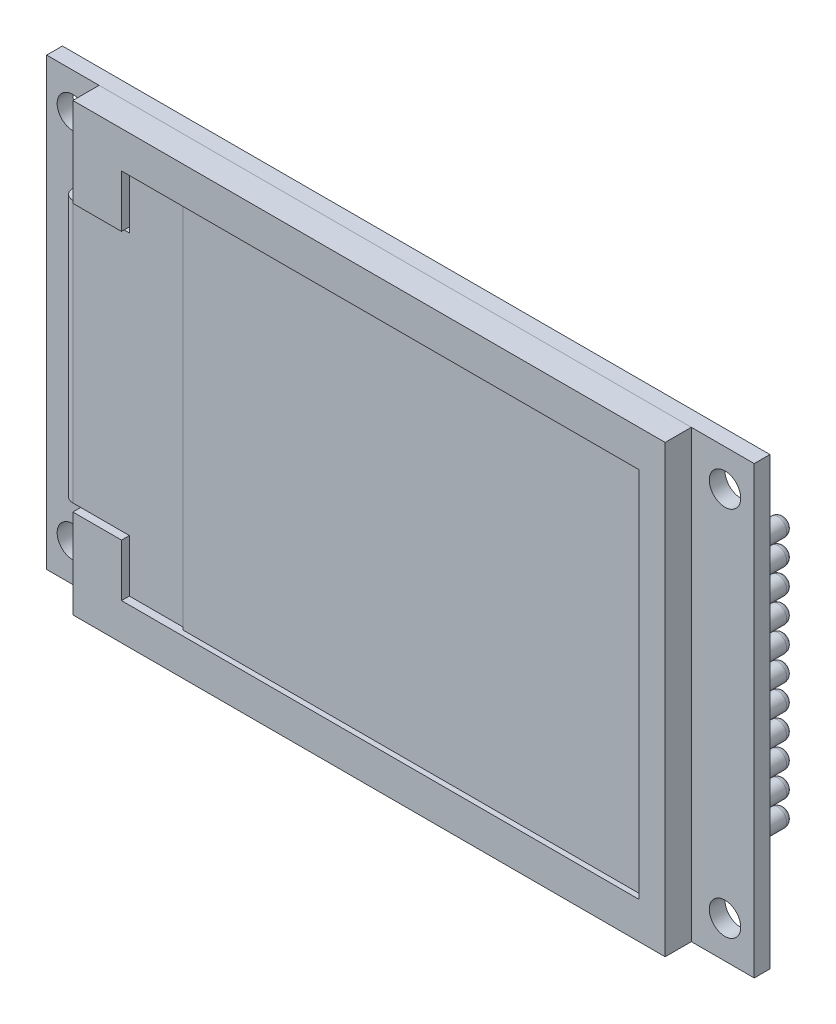
SolidWorks part; units mm, degrees
ref_plane "Front Plane" through (0, 0, 0) normal (0, 0, 1) x (1, 0, 0)
ref_plane "Top Plane" through (0, 0, 0) normal (0, 1, 0) x (1, 0, 0)
ref_plane "Right Plane" through (0, 0, 0) normal (1, 0, 0) x (0, 0, -1)
sketch "Sketch2" plane through (0, 0, 0) normal (0, 0, 1) x (1, 0, 0)
  line L1 (33.75, 21.25) -> (-33.75, 21.25)
  line L2 (33.75, 21.25) -> (33.75, -21.25)
  line L3 (33.75, -21.25) -> (-33.75, -21.25)
  line L4 (-33.75, 21.25) -> (-33.75, -21.25)
  line L5 (33.75, 21.25) -> (-33.75, -21.25) construction
  line L6 (33.75, -21.25) -> (-33.75, 21.25) construction
  point P0 (0, 0)
  dimension "D1" = 67.5
  dimension "D2" = 42.5
extrude "Boss-Extrude1" add sketch "Sketch2" along normal blind 1.5
sketch "Sketch3" plane through (0, 0, 1.5) normal (0, 0, 1) x (1, 0, 0)
  line L0 (33.75, 21.25) -> (-33.75, 21.25) construction
  line L1 (-33.75, 21.25) -> (-33.75, -21.25) construction
  circle A0 centre (-31.25, 17.75) radius 1.5
  circle A1 centre (30.96, 17.75) radius 1.5
  circle A2 centre (-31.25, -17.71) radius 1.5
  circle A3 centre (30.96, -17.71) radius 1.5
  dimension "D1" = 3
  dimension "D2" = 3.5
  dimension "D3" = 2.5
  dimension "D4" = 2
  dimension "D5" = 2
extrude "Cut-Extrude1" cut sketch "Sketch3" against normal through all
sketch "Sketch4" plane through (0, 0, 1.5) normal (0, 0, 1) x (1, 0, 0)
  line L0 (33.75, 21.25) -> (-33.75, 21.25) construction
  line L1 (-28.75, 21.25) -> (27.75, 21.25)
  line L2 (-28.75, 21.25) -> (-28.75, -21.25)
  line L3 (-28.75, -21.25) -> (27.75, -21.25)
  line L4 (27.75, 21.25) -> (27.75, -21.25)
  line L5 (-33.75, -21.25) -> (33.75, -21.25) construction
  line L6 (-33.75, 21.25) -> (-33.75, -21.25) construction
  line L7 (33.75, -21.25) -> (33.75, 21.25) construction
  dimension "D1" = 5
  dimension "D2" = 6
extrude "Boss-Extrude2" add sketch "Sketch4" along normal blind 2.5 separate body
sketch "Sketch5" plane through (0, 0, 4) normal (0, 0, 1) x (1, 0, 0)
  line L1 (-18.75, 17.75) -> (25.25, 17.75)
  line L2 (-18.75, 17.75) -> (-18.75, -17.75)
  line L3 (-18.75, -17.75) -> (25.25, -17.75)
  line L4 (25.25, 17.75) -> (25.25, -17.75)
  line L5 (27.75, -21.25) -> (27.75, 21.25) construction
  dimension "D2" = 44
  dimension "D3" = 35.5
  dimension "D4" = 17.75
  dimension "D5" = 2.5
extrude "Cut-Extrude2" cut sketch "Sketch5" against normal blind 0.5
sketch "Sketch6" plane through (0, 0, 4) normal (0, 0, 1) x (1, 0, 0)
  line L0 (-18.75, 17.75) -> (-24.1097, 17.75)
  line L1 (-24.1097, 17.75) -> (-24.1097, 12.75)
  line L2 (-24.1097, 12.75) -> (-28.75, 12.75)
  line L3 (-28.75, 21.25) -> (-28.75, -21.25) construction
  line L4 (-28.75, 12.75) -> (-28.75, -12.75)
  line L5 (-28.75, -12.75) -> (-24.1097, -12.75)
  line L6 (-24.1097, -12.75) -> (-24.1097, -17.75)
  line L7 (-24.1097, -17.75) -> (-18.75, -17.75)
  line L8 (-18.75, 17.75) -> (-18.75, -17.75)
  dimension "D1" = 0
  dimension "D2" = 5
  dimension "D3" = 5
extrude "Cut-Extrude3" cut sketch "Sketch6" against normal blind 1.5
sketch "Sketch7" plane through (0, 0, 2.5) normal (0, 0, 1) x (1, 0, 0)
  line L0 (-18.75, 17.5) -> (-23.8597, 17.5)
  line L1 (-18.75, -17.75) -> (-18.75, 17.75) construction
  line L2 (-23.8597, 17.5) -> (-23.8597, 12.5)
  line L3 (-23.8597, 12.5) -> (-30.25, 12.5)
  line L4 (-30.25, 12.5) -> (-30.25, -12.5)
  line L5 (-30.25, -12.5) -> (-23.8597, -12.5)
  line L6 (-23.8597, -12.5) -> (-23.8597, -17.5)
  line L7 (-23.8597, -17.5) -> (-18.75, -17.5)
  line L8 (-18.75, -17.5) -> (-18.75, 17.5)
  line L9 (-18.75, 17.75) -> (-24.1097, 17.75) construction
  line L10 (-24.1097, 17.75) -> (-24.1097, 12.75) construction
  line L11 (-24.1097, 12.75) -> (-28.75, 12.75) construction
  line L12 (-28.75, 12.75) -> (-28.75, -12.75) construction
  line L13 (-28.75, -12.75) -> (-24.1097, -12.75) construction
  line L14 (-24.1097, -12.75) -> (-24.1097, -17.75) construction
  line L15 (-24.1097, -17.75) -> (-18.75, -17.75) construction
  dimension "D1" = 0.25
  dimension "D2" = 0.25
  dimension "D3" = 0.25
  dimension "D4" = 1.5
  dimension "D5" = 0.25
  dimension "D6" = 0.25
  dimension "D7" = 0.25
extrude "Boss-Extrude3" add sketch "Sketch7" along normal blind 1 separate body
fillet "Fillet1" radius 1 1 edges at (-30.25, 0, 3.5)
sketch "Sketch8" plane through (0, 0, 0) normal (0, 0, -1) x (-1, 0, 0)
  line L0 (33.75, -21.25) -> (-33.75, -21.25) construction
  line L1 (18.75, -21.25) -> (-7.25, -21.25)
  line L2 (18.75, -21.25) -> (18.75, -11.3966)
  line L3 (-7.25, -4.25) -> (15.75, -4.25)
  line L4 (-7.25, -21.25) -> (-7.25, -4.25)
  line L5 (33.75, 21.25) -> (33.75, -21.25) construction
  line L6 (15.75, -4.25) -> (15.75, -8.4749)
  line L7 (15.75, -8.4749) -> (18.75, -11.3966)
  dimension "D1" = 15
  dimension "D2" = 17
  dimension "D3" = 23
  dimension "D4" = 26
extrude "Boss-Extrude4" add sketch "Sketch8" along normal blind 3 separate body
shell "Shell1" thickness 0.4 removed face at (-5.75, -21.25, -1.5)
sketch "Sketch9" plane through (0, 0, 0) normal (0, 0, -1) x (-1, 0, 0)
  line L0 (-33.75, -21.25) -> (-33.75, 21.25) construction
  line L1 (-32.46, -13.75) -> (-29.75, -13.75)
  line L2 (-32.46, -13.75) -> (-32.46, 13.75)
  line L3 (-32.46, 13.75) -> (-29.75, 13.75)
  line L4 (-29.75, -13.75) -> (-29.75, 13.75)
  line L5 (33.75, -21.25) -> (-33.75, -21.25) construction
  line L6 (-33.75, 21.25) -> (33.75, 21.25) construction
  circle A0 centre (-30.96, -17.71) radius 1.5 construction
  dimension "D4" = 1.5
  dimension "D1" = 4
  dimension "D2" = 7.5
  dimension "D3" = 7.5
extrude "Boss-Extrude5" add sketch "Sketch9" along normal blind 1 separate body
sketch "Sketch10" plane through (0, 0, -1) normal (0, 0, -1) x (-1, 0, 0)
  line L0 (-29.75, -13.75) -> (-29.75, 13.75) construction
  line L1 (-29.75, 13.75) -> (-32.46, 13.75) construction
  circle A0 centre (-31.1, 12.25) radius 0.85
  circle A1 centre (-31.1, 9.85) radius 0.85
  circle A2 centre (-31.1, 7.45) radius 0.85
  circle A3 centre (-31.1, 5.05) radius 0.85
  circle A4 centre (-31.1, 2.65) radius 0.85
  circle A5 centre (-31.1, 0.25) radius 0.85
  circle A6 centre (-31.1, -2.15) radius 0.85
  circle A7 centre (-31.1, -4.55) radius 0.85
  circle A8 centre (-31.1, -6.95) radius 0.85
  circle A9 centre (-31.1, -9.35) radius 0.85
  circle A10 centre (-31.1, -11.75) radius 0.85
  dimension "D1" = 1.35
  dimension "D2" = 1.7
  dimension "D3" = 1.5
  dimension "D4" = 11
extrude "Boss-Extrude6" add sketch "Sketch10" along normal blind 3
fillet "Fillet2" radius 0.6 11 edges at (30.25, -11.75, -4) (30.25, -9.35, -4) (30.25, -6.95, -4) (30.25, -4.55, -4) (30.25, -2.15, -4) (30.25, 0.25, -4) (30.25, 2.65, -4) (30.25, 5.05, -4) (30.25, 7.45, -4) (30.25, 9.85, -4) (30.25, 12.25, -4)
